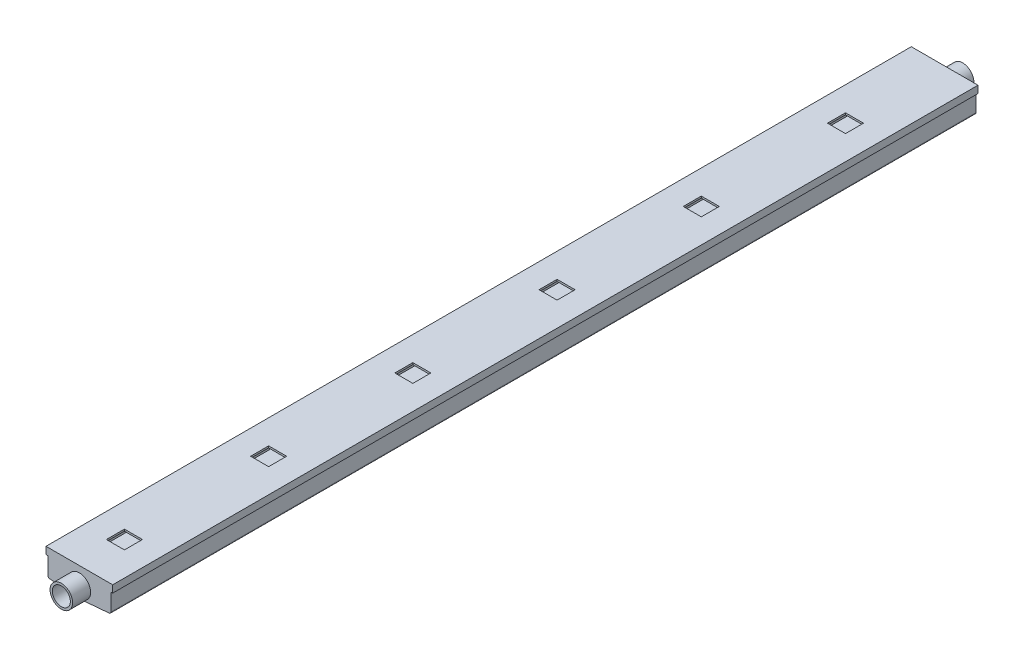
SolidWorks part; units mm, degrees
material "PVC Rigid"
ref_plane "Front Plane" through (0, 0, 0) normal (0, 0, 1) x (1, 0, 0)
ref_plane "Top Plane" through (0, 0, 0) normal (0, 1, 0) x (1, 0, 0)
ref_plane "Right Plane" through (0, 0, 0) normal (1, 0, 0) x (0, 0, -1)
other "Center of Mass"
sketch "Sketch1" plane through (0, 0, 0) normal (0, 0, 1) x (1, 0, 0)
  line L2 (0, 0) -> (0, 34.29)
  line L3 (0, 34.29) -> (88.9, 34.29)
  line L4 (88.9, 0) -> (88.9, 34.29)
  line L5 (0, 0) -> (44.45, -3.81)
  line L6 (44.45, -3.81) -> (88.9, 0)
  point P5 (44.45, 34.29)
  dimension "D1" = 34.29
  dimension "D2" = 88.9
  dimension "D3" = 38.1
extrude "Boss-Extrude1" add sketch "Sketch1" along normal blind 1219.2
sketch "Sketch2" plane through (88.9, 0, 0) normal (1, 0, 0) x (0, 0, -1)
  line L0 (0, 0) -> (0, 34.29) construction
  line L1 (-1219.2, 34.29) -> (0, 34.29)
  line L2 (-1219.2, 34.29) -> (-1219.2, 26.67)
  line L3 (-1219.2, 26.67) -> (0, 26.67)
  line L4 (0, 34.29) -> (0, 26.67)
  dimension "D1" = 7.62
extrude "Boss-Extrude2" add sketch "Sketch2" along normal blind 2.54
sketch "Sketch3" plane through (0, 0, 0) normal (-1, 0, 0) x (0, 0, 1)
  line L0 (1219.2, 34.29) -> (1219.2, 0) construction
  line L1 (0, 34.29) -> (1219.2, 34.29)
  line L2 (0, 34.29) -> (0, 26.67)
  line L3 (0, 26.67) -> (1219.2, 26.67)
  line L4 (1219.2, 34.29) -> (1219.2, 26.67)
  dimension "D1" = 7.62
extrude "Boss-Extrude3" add sketch "Sketch3" along normal blind 2.54
sketch "Sketch4" plane through (0, 0, 0) normal (0, 0, -1) x (-1, 0, 0)
  circle A0 centre (-44.45, 12.065) radius 15.875
  circle A1 centre (-44.45, 12.065) radius 12.7
  dimension "D1" = 31.75
  dimension "D2" = 25.4
extrude "Boss-Extrude4" add sketch "Sketch4" along normal blind 25.4
sketch "Sketch5" plane through (0, 0, 0) normal (0, 0, -1) x (-1, 0, 0)
  circle A1 centre (-44.45, 12.065) radius 12.7
sketch "Sketch6" plane through (0, 0, 1219.2) normal (0, 0, 1) x (1, 0, 0)
  circle A0 centre (44.45, 12.065) radius 15.875
  circle A1 centre (44.45, 12.065) radius 12.7
  dimension "D1" = 31.75
extrude "Boss-Extrude5" add sketch "Sketch6" along normal blind 25.4
shell "Shell2" thickness 2.54 removed face at (44.45, 34.29, 609.6)
sketch "Sketch9" plane through (0, 34.29, 0) normal (0, 1, 0) x (1, 0, 0)
  line L1 (-2.54, -1219.2) -> (91.44, -1219.2)
  line L2 (-2.54, -1219.2) -> (-2.54, 0)
  line L3 (-2.54, 0) -> (91.44, 0)
  line L4 (91.44, -1219.2) -> (91.44, 0)
extrude "Boss-Extrude7" add sketch "Sketch9" along normal blind 2.54
fillet "Fillet1" radius 2.54 2 edges at (0, 0, 609.6) (88.9, 0, 609.6)
extrude "Cut-Extrude3" cut sketch "Sketch5" against normal up to next contours A1
sketch "Sketch11" plane through (0, 0, 1219.2) normal (0, 0, 1) x (1, 0, 0)
  circle A1 centre (44.45, 12.065) radius 12.7
extrude "Cut-Extrude4" cut sketch "Sketch11" against normal blind 2.54
sketch "Sketch12" plane through (0, 36.83, 0) normal (0, 1, 0) x (1, 0, 0)
  line L0 (44.45, -1219.2) -> (44.45, -1090.339) construction
  line L1 (-2.54, -1219.2) -> (91.44, -1219.2) construction
  line L3 (57.15, -1168.4) -> (31.75, -1168.4)
  line L4 (57.15, -1168.4) -> (57.15, -1143)
  line L5 (57.15, -1143) -> (31.75, -1143)
  line L6 (31.75, -1168.4) -> (31.75, -1143)
  line L7 (57.15, -1168.4) -> (31.75, -1143) construction
  line L8 (57.15, -1143) -> (31.75, -1168.4) construction
  point P4 (44.45, -1155.7)
  dimension "D1" = 25.4
  dimension "D2" = 50.8
extrude "Cut-Extrude5" cut sketch "Sketch12" against normal up to next
pattern_linear "LPattern1" count 6 spacing 203.2 along (0, 0, -1) of "Cut-Extrude5"
